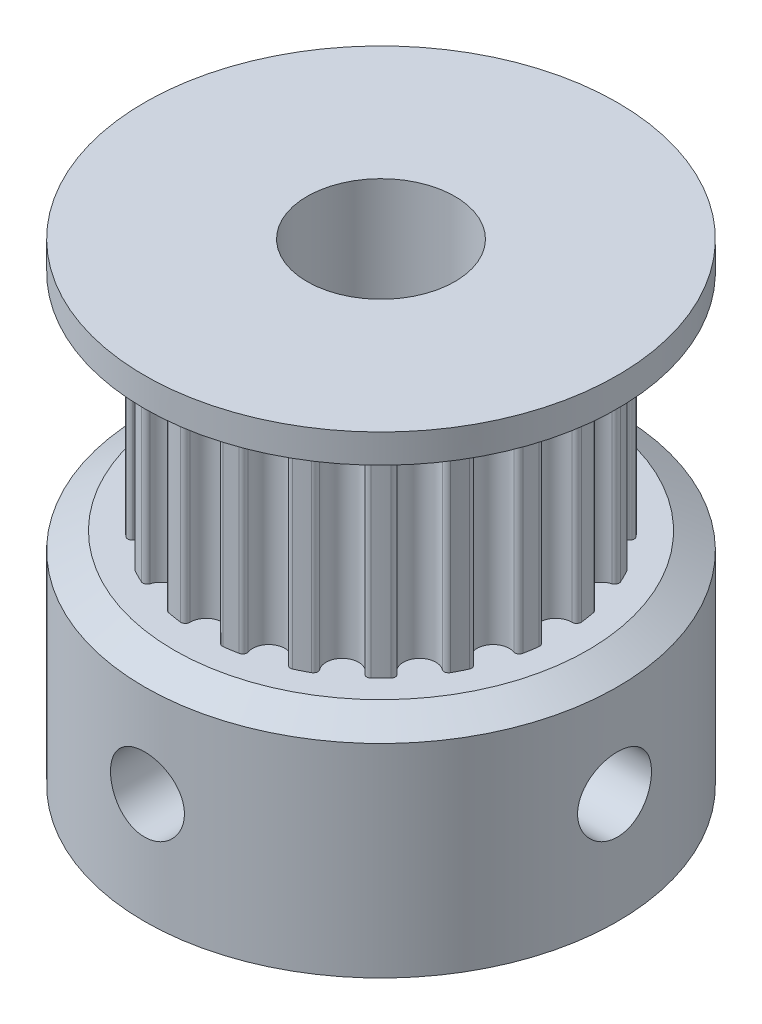
SolidWorks part; units mm, degrees
note: '?' marks a value the reader was unsure of.
material "1060 Сплав"
ref_plane "Спереди" through (0, 0, 0) normal (0, 0, 1) x (1, 0, 0)
ref_plane "Сверху" through (0, 0, 0) normal (0, 1, 0) x (1, 0, 0)
ref_plane "Справа" through (0, 0, 0) normal (1, 0, 0) x (0, 0, -1)
other "Configuration Table"
sketch "Эскиз1" plane through (0, 0, 0) normal (0, 1, 0) x (1, 0, 0)
  circle A0 centre (0, 0) radius 8
  circle A1 centre (0, 0) radius 2.5
  dimension "D1" = 16
  dimension "D2" = 5
extrude "Бобышка-Вытянуть1" add sketch "Эскиз1" along normal blind 7.45
sketch "Эскиз2" plane through (0, 7.45, 0) normal (0, 1, 0) x (1, 0, 0)
  arc A0 (-2.5575, 5.549) -> (-2.986, 5.3307) centre (0, 0) ccw
  circle A1 centre (0, 0) radius 2.5 construction
  circle A2 centre (0, 0) radius 2.5
  arc A3 (-0.55, 5.9169) -> (0.55, 5.9169) centre (0, 5.91) ccw
  arc A4 (1.3054, 5.7972) -> (2.3515, 5.4573) centre (1.8263, 5.6207) ccw
  arc A5 (3.0329, 5.1101) -> (3.9228, 4.4636) centre (3.4738, 4.7813) ccw
  arc A6 (4.4636, 3.9228) -> (5.1101, 3.0329) centre (4.7813, 3.4738) ccw
  arc A7 (5.4573, 2.3515) -> (5.7972, 1.3054) centre (5.6207, 1.8263) ccw
  arc A8 (5.9169, 0.55) -> (5.9169, -0.55) centre (5.91, 0) ccw
  arc A9 (5.7972, -1.3054) -> (5.4573, -2.3515) centre (5.6207, -1.8263) ccw
  arc A10 (5.1101, -3.0329) -> (4.4636, -3.9228) centre (4.7813, -3.4738) ccw
  arc A11 (3.9228, -4.4636) -> (3.0329, -5.1101) centre (3.4738, -4.7813) ccw
  arc A12 (2.3515, -5.4573) -> (1.3054, -5.7972) centre (1.8263, -5.6207) ccw
  arc A13 (0.55, -5.9169) -> (-0.55, -5.9169) centre (0, -5.91) ccw
  arc A14 (-1.3054, -5.7972) -> (-2.3515, -5.4573) centre (-1.8263, -5.6207) ccw
  arc A15 (-3.0329, -5.1101) -> (-3.9228, -4.4636) centre (-3.4738, -4.7813) ccw
  arc A16 (-4.4636, -3.9228) -> (-5.1101, -3.0329) centre (-4.7813, -3.4738) ccw
  arc A17 (-5.4573, -2.3515) -> (-5.7972, -1.3054) centre (-5.6207, -1.8263) ccw
  arc A18 (-5.9169, -0.55) -> (-5.9169, 0.55) centre (-5.91, 0) ccw
  arc A19 (-5.7972, 1.3054) -> (-5.4573, 2.3515) centre (-5.6207, 1.8263) ccw
  arc A20 (-5.1101, 3.0329) -> (-4.4636, 3.9228) centre (-4.7813, 3.4738) ccw
  arc A21 (-3.9228, 4.4636) -> (-3.0329, 5.1101) centre (-3.4738, 4.7813) ccw
  arc A22 (-2.3515, 5.4573) -> (-1.3054, 5.7972) centre (-1.8263, 5.6207) ccw
  arc A23 (-4.147, 4.4871) -> (-4.4871, 4.147) centre (0, 0) ccw
  arc A24 (-0.7176, 6.0677) -> (-1.1926, 5.9925) centre (0, 0) ccw
  arc A25 (1.1926, 5.9925) -> (0.7176, 6.0677) centre (0, 0) ccw
  arc A26 (2.986, 5.3307) -> (2.5575, 5.549) centre (0, 0) ccw
  arc A27 (4.4871, 4.147) -> (4.147, 4.4871) centre (0, 0) ccw
  arc A28 (5.549, 2.5575) -> (5.3307, 2.986) centre (0, 0) ccw
  arc A29 (6.0677, 0.7176) -> (5.9925, 1.1926) centre (0, 0) ccw
  arc A30 (-5.3307, 2.986) -> (-5.549, 2.5575) centre (0, 0) ccw
  arc A31 (-5.9925, 1.1926) -> (-6.0677, 0.7176) centre (0, 0) ccw
  arc A32 (-6.0677, -0.7176) -> (-5.9925, -1.1926) centre (0, 0) ccw
  arc A33 (-5.549, -2.5575) -> (-5.3307, -2.986) centre (0, 0) ccw
  arc A34 (-4.4871, -4.147) -> (-4.147, -4.4871) centre (0, 0) ccw
  arc A35 (-2.986, -5.3307) -> (-2.5575, -5.549) centre (0, 0) ccw
  arc A36 (5.9925, -1.1926) -> (6.0677, -0.7176) centre (0, 0) ccw
  arc A37 (5.3307, -2.986) -> (5.549, -2.5575) centre (0, 0) ccw
  arc A38 (4.147, -4.4871) -> (4.4871, -4.147) centre (0, 0) ccw
  arc A39 (2.5575, -5.549) -> (2.986, -5.3307) centre (0, 0) ccw
  arc A40 (0.7176, -6.0677) -> (1.1926, -5.9925) centre (0, 0) ccw
  arc A41 (-1.1926, -5.9925) -> (-0.7176, -6.0677) centre (0, 0) ccw
  arc A42 (5.9169, 0.55) -> (6.0677, 0.7176) centre (5.9188, 0.6999) ccw
  arc A43 (5.7972, 1.3054) -> (5.9925, 1.1926) centre (5.8454, 1.1633) cw
  arc A44 (5.4573, 2.3515) -> (5.549, 2.5575) centre (5.4128, 2.4947) ccw
  arc A45 (5.1101, 3.0329) -> (5.3307, 2.986) centre (5.1998, 2.9127) cw
  arc A46 (5.1101, -3.0329) -> (5.3307, -2.986) centre (5.1998, -2.9127) ccw
  arc A47 (5.4573, -2.3515) -> (5.549, -2.5575) centre (5.4128, -2.4947) cw
  arc A48 (5.7972, -1.3054) -> (5.9925, -1.1926) centre (5.8454, -1.1633) ccw
  arc A49 (5.9169, -0.55) -> (6.0677, -0.7176) centre (5.9188, -0.6999) cw
  arc A50 (3.9228, -4.4636) -> (4.147, -4.4871) centre (4.0452, -4.377) ccw
  arc A51 (4.4636, -3.9228) -> (4.4871, -4.147) centre (4.377, -4.0452) cw
  arc A52 (3.0329, -5.1101) -> (2.986, -5.3307) centre (2.9127, -5.1998) cw
  arc A53 (1.3054, -5.7972) -> (1.1926, -5.9925) centre (1.1633, -5.8454) cw
  arc A54 (0.55, -5.9169) -> (0.7176, -6.0677) centre (0.6999, -5.9188) ccw
  arc A55 (-0.55, -5.9169) -> (-0.7176, -6.0677) centre (-0.6999, -5.9188) cw
  arc A56 (-1.3054, -5.7972) -> (-1.1926, -5.9925) centre (-1.1633, -5.8454) ccw
  arc A57 (-2.3515, -5.4573) -> (-2.5575, -5.549) centre (-2.4947, -5.4128) cw
  arc A58 (-3.0329, -5.1101) -> (-2.986, -5.3307) centre (-2.9127, -5.1998) ccw
  arc A59 (-3.9228, -4.4636) -> (-4.147, -4.4871) centre (-4.0452, -4.377) cw
  arc A60 (-4.4636, -3.9228) -> (-4.4871, -4.147) centre (-4.377, -4.0452) ccw
  arc A61 (-5.9169, -0.55) -> (-6.0677, -0.7176) centre (-5.9188, -0.6999) ccw
  arc A62 (-5.7972, -1.3054) -> (-5.9925, -1.1926) centre (-5.8454, -1.1633) cw
  arc A63 (-5.4573, -2.3515) -> (-5.549, -2.5575) centre (-5.4128, -2.4947) ccw
  arc A64 (-5.1101, -3.0329) -> (-5.3307, -2.986) centre (-5.1998, -2.9127) cw
  arc A65 (-5.1101, 3.0329) -> (-5.3307, 2.986) centre (-5.1998, 2.9127) ccw
  arc A66 (-5.4573, 2.3515) -> (-5.549, 2.5575) centre (-5.4128, 2.4947) cw
  arc A67 (-5.7972, 1.3054) -> (-5.9925, 1.1926) centre (-5.8454, 1.1633) ccw
  arc A68 (-5.9169, 0.55) -> (-6.0677, 0.7176) centre (-5.9188, 0.6999) cw
  arc A69 (-4.4636, 3.9228) -> (-4.4871, 4.147) centre (-4.377, 4.0452) cw
  arc A70 (-3.9228, 4.4636) -> (-4.147, 4.4871) centre (-4.0452, 4.377) ccw
  arc A71 (-3.0329, 5.1101) -> (-2.986, 5.3307) centre (-2.9127, 5.1998) cw
  arc A72 (-2.3515, 5.4573) -> (-2.5575, 5.549) centre (-2.4947, 5.4128) ccw
  arc A73 (-1.3054, 5.7972) -> (-1.1926, 5.9925) centre (-1.1633, 5.8454) cw
  arc A74 (-0.55, 5.9169) -> (-0.7176, 6.0677) centre (-0.6999, 5.9188) ccw
  arc A75 (4.4636, 3.9228) -> (4.4871, 4.147) centre (4.377, 4.0452) ccw
  arc A76 (3.9228, 4.4636) -> (4.147, 4.4871) centre (4.0452, 4.377) cw
  arc A77 (0.55, 5.9169) -> (0.7176, 6.0677) centre (0.6999, 5.9188) cw
  arc A78 (1.3054, 5.7972) -> (1.1926, 5.9925) centre (1.1633, 5.8454) ccw
  arc A79 (3.0329, 5.1101) -> (2.986, 5.3307) centre (2.9127, 5.1998) ccw
  arc A80 (2.3515, 5.4573) -> (2.5575, 5.549) centre (2.4947, 5.4128) cw
  arc A81 (2.3515, -5.4573) -> (2.5575, -5.549) centre (2.4947, -5.4128) ccw
  point P69 (0, 0)
  point P135 (-0.5205, 6.0878)
  point P142 (0.5205, 6.0878)
  dimension "D1" = 12.22
  dimension "D2" = 1.1
  dimension "D3" = 0.75
  dimension "D5" = 0.15
  dimension "D6" = 0.15
  dimension "D4" = 20
extrude "Бобышка-Вытянуть2" add sketch "Эскиз2" along normal blind 7
sketch "Эскиз3" plane through (0, 14.45, 0) normal (0, 1, 0) x (1, 0, 0)
  circle A0 centre (0, 0) radius 2.5 construction
  circle A1 centre (0, 0) radius 2.5
  circle A2 centre (0, 0) radius 8 construction
  circle A3 centre (0, 0) radius 8
extrude "Бобышка-Вытянуть3" add sketch "Эскиз3" along normal blind 1.55
sketch "Эскиз4" plane through (0, 0, 0) normal (0, 0, 1) x (1, 0, 0)
  line L0 (-8, 3.725) -> (8, 3.725) construction
  line L1 (-8, 7.45) -> (-8, 0) construction
  line L2 (8, 0) -> (8, 7.45) construction
  circle A0 centre (0, 3.725) radius 1.25
  dimension "D1" = 2.5
extrude "Вырез-Вытянуть1" cut sketch "Эскиз4" along normal up to surface (7.9017 mm away)
sketch "Эскиз5" plane through (0, 0, 0) normal (1, 0, 0) x (0, 0, -1)
  line L0 (8, 3.725) -> (-7.9017, 3.725) construction
  line L1 (8, 0) -> (8, 7.45) construction
  circle A0 centre (0, 3.725) radius 1.25
  spline S1 degree 2 poles (-8, 4.975) (-7.8047, 3.725) (-8, 2.475) knots 0 0 0 1 1 1 weights 0.00675 0.008 0.00925 construction
  dimension "D1" = 2.5
extrude "Вырез-Вытянуть2" cut sketch "Эскиз5" along normal up to surface (7.9017 mm away)
sketch "Минимальный радиус ремня" plane through (0, 7.45, 0) normal (0, 1, 0) x (1, 0, 0)
  circle A0 centre (0, 0) radius 5.36
  arc A2 (-2.986, -5.3307) -> (-2.5575, -5.549) centre (0, 0) ccw construction
  dimension "D1" = 0.75
  dimension "D2" = 10.72
chamfer "Фаска1" distance 1 angle 30 2 edges at (0, 14.45, 8) (0, 7.45, 8)
ref_axis "Ось1" through (0, 16, 0) along (0, -1, 0)?
